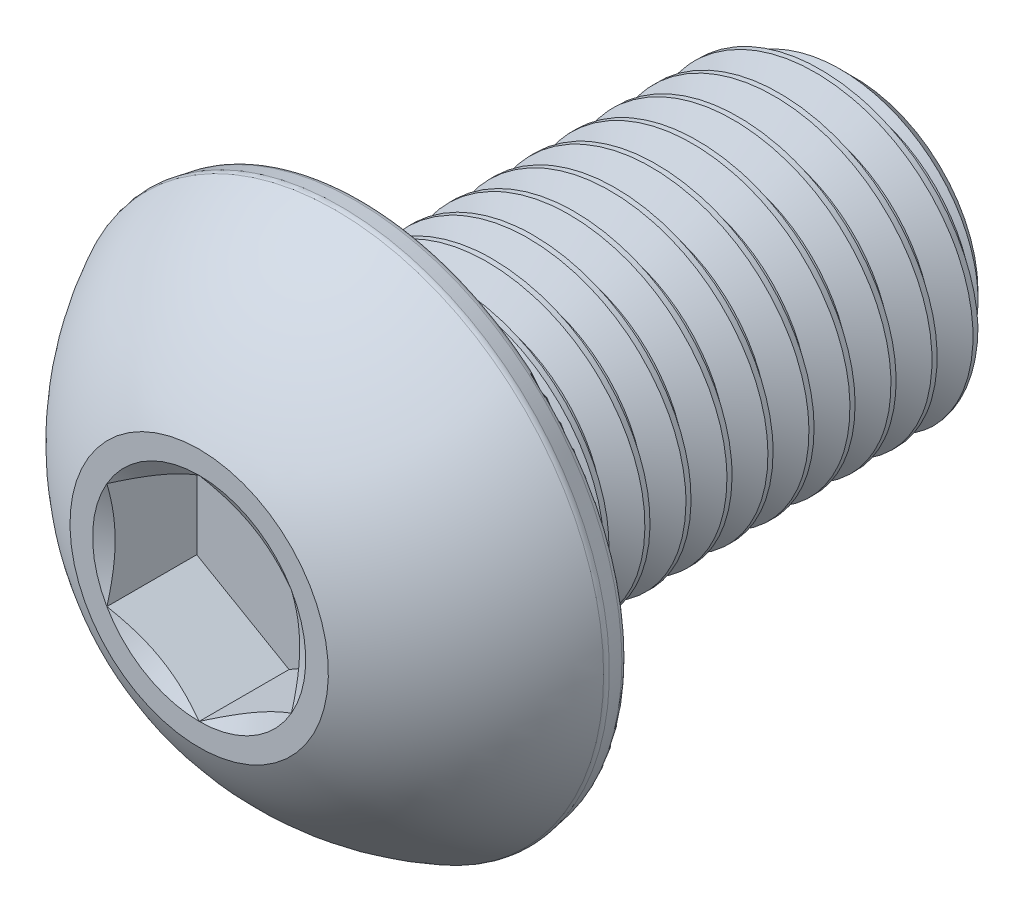
SolidWorks part; units mm, degrees
material "Alloy Steel"
ref_plane "Front Plane" through (0, 0, 0) normal (0, 0, 1) x (1, 0, 0)
ref_plane "Top Plane" through (0, 0, 0) normal (0, 1, 0) x (1, 0, 0)
ref_plane "Right Plane" through (0, 0, 0) normal (1, 0, 0) x (0, 0, -1)
sketch "Sketch1" plane through (0, 0, 0) normal (1, 0, 0) x (0, 0, -1)
  line L0 (-8.4582, 0) -> (8.4582, 0) construction
  line L1 (-8.4582, 0) -> (-8.4582, 6.9469)
  line L2 (-8.4582, 6.9469) -> (-4.2418, 6.9469)
  line L3 (-4.2418, 6.9469) -> (-4.2418, 3.9751)
  line L4 (-4.2418, 3.9751) -> (8.4582, 3.9751)
  line L5 (8.4582, 3.9751) -> (8.4582, 0)
  point P2 (0, 0)
  point P4 (7.3999, 0)
  point P9 (6.8707, 3.9751)
  point P10 (6.8707, -3.9751)
  point P11 (8.4582, -3.9751)
  point P15 (-6.1392, 0)
  dimension "Head Height" = 4.2164
  dimension "Head Diameter" = 13.8938
  dimension "Length" = 12.7
  dimension "Screw Size Decimal Equivalent" = 7.9502
  dimension "Thread Pitch" = 1.0583
  dimension "D1" = 1.5875
  dimension "D2" = 2.319
sketch "Sketch2" plane through (0, 0, 0) normal (0, 0, 1) x (1, 0, 0)
  line L0 (0, 3.9751) -> (0, 0) construction
  line L1 (0, 2.7496) -> (-2.3813, 1.3748)
  line L2 (-2.3813, 1.3748) -> (-2.3812, -1.3748)
  line L3 (-2.3812, -1.3748) -> (0, -2.7496)
  line L4 (0, -2.7496) -> (2.3813, -1.3748)
  line L5 (2.3813, -1.3748) -> (2.3813, 1.3748)
  line L6 (2.3813, 1.3748) -> (0, 2.7496)
  circle A0 centre (0, 0) radius 2.3813 construction
  circle A1 centre (0, 0) radius 3.3337
  point P10 (0, 3.3337)
  dimension "D1" = 6.6675
  dimension "Drive Size" = 4.7625
sketch "Sketch3" plane through (0, 0, 0) normal (1, 0, 0) x (0, 0, -1)
  line L0 (-8.4582, 0) -> (-8.4582, 3.3337)
  line L1 (-8.4582, 0) -> (-8.4582, 6.9469) construction
  line L2 (-8.4582, 6.9469) -> (-4.2418, 6.9469) construction
  line L3 (-4.8743, 6.9469) -> (-4.2418, 6.8354)
  line L4 (-4.2418, 6.9469) -> (-4.2418, 3.9751) construction
  line L5 (-4.2418, 6.8354) -> (-4.2418, 3.9751)
  line L6 (-8.4582, 0) -> (8.4582, 0) construction
  line L7 (-8.4582, 0) -> (8.4582, 0)
  line L8 (8.4582, 0) -> (8.4582, 3.1813)
  line L9 (8.4582, 3.9751) -> (8.4582, 0) construction
  line L10 (8.4582, 3.1813) -> (7.6644, 3.9751)
  line L11 (-4.2418, 3.9751) -> (8.4582, 3.9751) construction
  line L12 (7.6644, 3.9751) -> (-4.2418, 3.9751)
  arc A0 (-8.4582, 3.3337) -> (-4.8743, 6.9469) centre (-1.484, 0) cw
  dimension "D1" = 0.6325
  dimension "D2" = 10
  dimension "D3" = 45
  dimension "D4" = 0.7938
revolve "Revolve1" add sketch "Sketch3" angle 360 about L7
sketch "Sketch4" plane through (0, 0, 8.4582) normal (0, 0, 1) x (1, 0, 0)
  line L0 (-2.3812, -1.3748) -> (0, -2.7496) construction
  line L1 (-2.3813, 1.3748) -> (-2.3812, -1.3748) construction
  line L2 (0, 2.7496) -> (-2.3813, 1.3748) construction
  line L3 (2.3813, 1.3748) -> (0, 2.7496) construction
  line L4 (2.3813, -1.3748) -> (2.3813, 1.3748) construction
  line L5 (0, -2.7496) -> (2.3813, -1.3748) construction
  line L6 (-2.3812, -1.3748) -> (0, -2.7496)
  line L7 (-2.3813, 1.3748) -> (-2.3812, -1.3748)
  line L8 (0, 2.7496) -> (-2.3813, 1.3748)
  line L9 (2.3813, 1.3748) -> (0, 2.7496)
  line L10 (2.3813, -1.3748) -> (2.3813, 1.3748)
  line L11 (0, -2.7496) -> (2.3813, -1.3748)
extrude "Cut-Extrude1" cut sketch "Sketch4" against normal up to vertex (2.319 mm away) up to point (0, 0, 6.1392)
sketch "Sketch5" plane through (0, 0, 8.4582) normal (0, 0, 1) x (1, 0, 0)
  circle A0 centre (0, 0) radius 2.7496
extrude "Cut-Extrude2" cut sketch "Sketch5" against normal up to vertex (2.319 mm away) draft 60 up to point (0, 0, 6.1392)
fillet "Fillet1" radius 0.2108 2 edges at (6.9469, 0, 4.8743) (6.8354, 0, 4.2418)
split "Split1" bodies to split 106 resulting bodies 107 108 split by face at (6.6585, 0, 4.2418)
sketch "Sketch6" plane through (0, 0, -8.4582) normal (0, 0, -1) x (-1, 0, 0)
  circle A0 centre (0, 0) radius 3.9751 construction
  circle A1 centre (0, 0) radius 3.9751
curve "Helix/Spiral1" pitch 1.0583 height 13.7583 radius 3.9751 centre (0, 0, -8.4582) axis (0, 0, 1) start towards (0, 1, 0)
sketch "Sketch7" plane through (0, 0, 0) normal (1, 0, 0) x (0, 0, -1)
  line L0 (8.3921, 4.0897) -> (8.9212, 3.1731) construction
  line L1 (8.9212, 3.1731) -> (9.4504, 4.0897) construction
  line L2 (9.4504, 4.0897) -> (8.3921, 4.0897) construction
  line L3 (8.4251, 4.0324) -> (9.4173, 4.0324)
  line L4 (9.4173, 4.0324) -> (8.9874, 3.2877)
  line L5 (8.9874, 3.2877) -> (8.8551, 3.2877)
  line L6 (8.8551, 3.2877) -> (8.4251, 4.0324)
  line L7 (8.9212, 3.2877) -> (8.9212, 3.1731) construction
  line L8 (8.4582, 3.9751) -> (9.3842, 3.9751) construction
  line L9 (8.9212, 4.0897) -> (8.9212, 3.9751) construction
  point P12 (8.9212, 4.0324)
  dimension "D1" = 1.0583
  dimension "D2" = 0.1323
sweep "Cut-Sweep1" cut profiles "Sketch7" path "Helix/Spiral1" align with end faces yes
sketch "Sketch8" plane through (0, 0, 4.2418) normal (0, 0, -1) x (-1, 0, 0)
  circle A0 centre (0, 0) radius 4.0897
extrude "Boss-Extrude1" add sketch "Sketch8" along normal up to vertex (11.1125 mm away) draft 45 up to point (0, 3.9751, -6.8707)
equation "\"D1@Sketch1\"=\"Thread Pitch@Sketch1\"*1.5"
equation "\"D2@Sketch1\"=0.55*\"Head Height@Sketch1\""
equation "\"D1@Sketch2\"=\"Drive Size@Sketch2\"*1.4"
equation "\"D1@Sketch3\"=0.15*\"Head Height@Sketch1\""
equation "\"D4@Sketch3\"=0.75*\"Thread Pitch@Sketch1\""
equation "\"D1@Fillet1\"=.05*\"Head Height@Sketch1\""
equation "\"D4@Helix/Spiral1\"=\"Thread Pitch@Sketch1\""
equation "\"D3@Helix/Spiral1\"=\"Length@Sketch1\"+\"Thread Pitch@Sketch1\""
equation "\"D2@Sketch7\"=\"D1@Sketch7\"/8"
equation "\"D1@Sketch7\"=\"Thread Pitch@Sketch1\""
